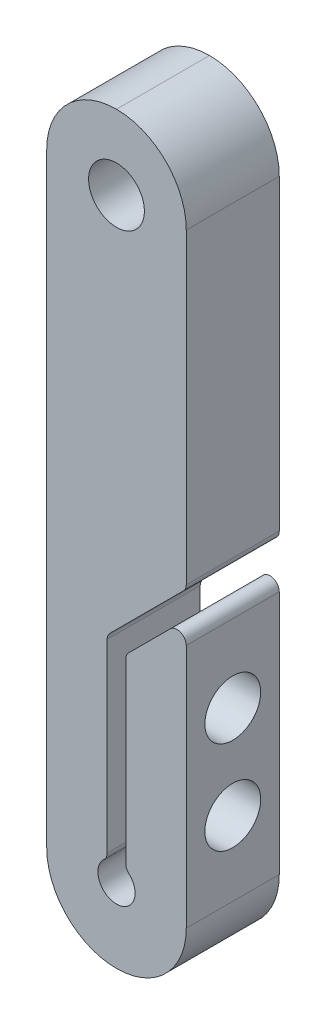
SolidWorks part; units mm, degrees
ref_plane "Front" through (0, 0, 0) normal (0, 0, 1) x (1, 0, 0)
ref_plane "Top" through (0, 0, 0) normal (0, 1, 0) x (1, 0, 0)
ref_plane "Right" through (0, 0, 0) normal (1, 0, 0) x (0, 0, -1)
sketch "Esquisse1" plane through (0, 0, 0) normal (0, 0, 1) x (1, 0, 0)
  line L1 (0, 0) -> (15, 0)
  line L2 (0, 0) -> (0, 80)
  line L3 (0, 80) -> (15, 80)
  line L4 (15, 0) -> (15, 80)
  dimension "D1" = 15
  dimension "D2" = 80
extrude "Boss.-Extru.1" add sketch "Esquisse1" along normal blind 10
sketch "Esquisse2" plane through (0, 0, 10) normal (0, 0, 1) x (1, 0, 0)
  line L0 (7.5, 80) -> (7.5, 81) construction
  line L1 (15, 80) -> (0, 80) construction
  line L2 (0, 0) -> (15, 0) construction
  line L3 (7.5, 8) -> (7.5, 0) construction
  circle A1 centre (7.5, 72) radius 3
  circle A2 centre (7.5, 8) radius 2
  point P11 (7.5, 0)
  dimension "D2" = 8
  dimension "D3" = 6
  dimension "D4" = 4
  dimension "D5" = 8
extrude "Enlèv. mat.-Extru.1" cut sketch "Esquisse2" against normal up to vertex (10 mm away) up to point (0, 80, 0)
fillet "Congé1" radius 7.5 4 edges at (15, 80, 5) (0, 80, 5) (15, 0, 5) (0, 0, 5)
sketch "Esquisse3" plane through (0, 0, 10) normal (0, 0, 1) x (1, 0, 0)
  line L0 (6.5, 9.7321) -> (6.5, 30.5605)
  line L1 (6.5, 30.5605) -> (15, 39.0605)
  line L2 (15, 7.5) -> (15, 72.5) construction
  line L3 (15, 39.0605) -> (15, 36.2321)
  line L4 (15, 36.2321) -> (8.5, 29.7321)
  line L5 (8.5, 29.7321) -> (8.5, 9.7321)
  line L6 (8.5, 9.7321) -> (6.5, 9.7321)
  line L7 (7.5, 10) -> (7.5, 9.7321) construction
  circle A0 centre (7.5, 8) radius 2 construction
  dimension "D1" = 2
  dimension "D2" = 2
  dimension "D3" = 20
  dimension "D4" = 135
extrude "Enlèv. mat.-Extru.2" cut sketch "Esquisse3" against normal through all
sketch "Esquisse4" plane through (15, 0, 0) normal (1, 0, 0) x (0, 0, -1)
  line L0 (-5, 7.5) -> (-5, 36.2321) construction
  line L1 (-10, 7.5) -> (0, 7.5) construction
  line L2 (0, 36.2321) -> (-10, 36.2321) construction
  circle A0 centre (-5, 15.5) radius 2.1
  circle A1 centre (-5, 25.5) radius 2.1
  dimension "D1" = 10
  dimension "D2" = 4.2
  dimension "D3" = 8
extrude "Enlèv. mat.-Extru.3" cut sketch "Esquisse4" against normal through all
sketch "Esquisse5" plane through (15, 0, 0) normal (1, 0, 0) x (0, 0, -1)
  circle A0 centre (-5, 25.5) radius 3
  circle A1 centre (-5, 15.5) radius 3
  dimension "D1" = 6
extrude "Enlèv. mat.-Extru.4" cut sketch "Esquisse5" against normal up to vertex (6.5 mm away) up to point (8.5, 29.7321, 0)
fillet "Congé2" radius 1 6 edges at (15, 36.2321, 5) (8.5, 9.7321, 5) (6.5, 9.7321, 5) (8.5, 29.7321, 5) (15, 39.0605, 5) (6.5, 30.5605, 5)
